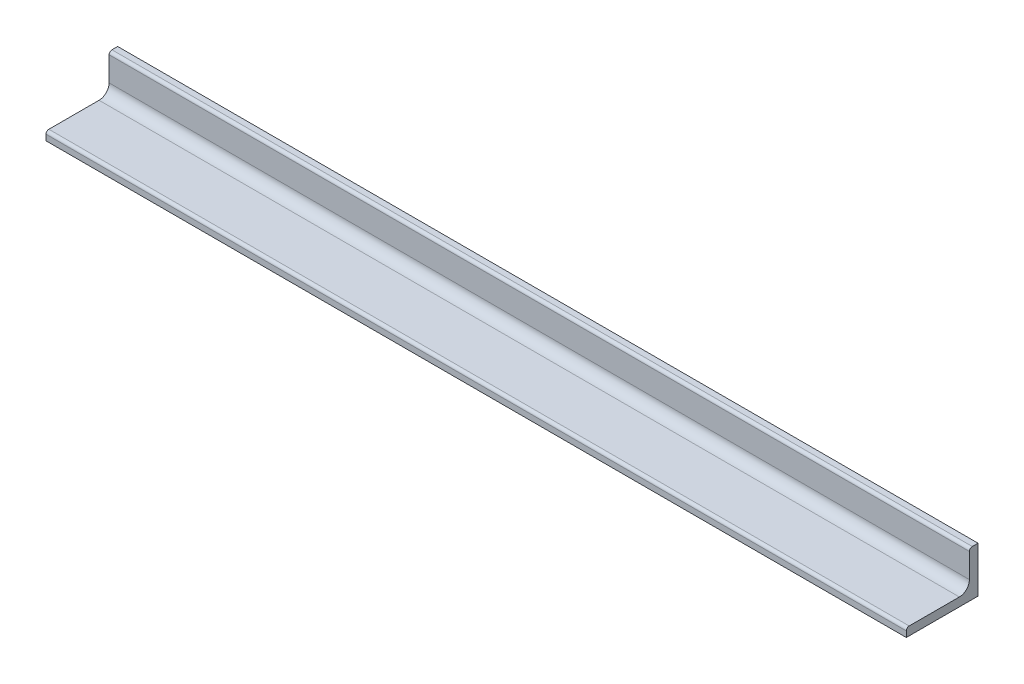
SolidWorks part; units mm, degrees
ref_plane "Front" through (0, 0, 0) normal (0, 0, 1) x (1, 0, 0)
ref_plane "Top" through (0, 0, 0) normal (0, 1, 0) x (1, 0, 0)
ref_plane "Right" through (0, 0, 0) normal (1, 0, 0) x (0, 0, -1)
sketch "Sketch1" plane through (0, 0, 0) normal (1, 0, 0) x (0, 1, 0)
  line L0 (0, 25) -> (0, 0)
  line L1 (0, 0) -> (16, 0)
  line L2 (3, 24) -> (3, 6.5)
  line L3 (6.5, 3) -> (15, 3)
  line L4 (0, 25) -> (2, 25)
  line L5 (16, 0) -> (16, 2)
  arc A0 (2, 25) -> (3, 24) centre (2, 24) cw
  arc A1 (16, 2) -> (15, 3) centre (15, 2) ccw
  arc A2 (3, 6.5) -> (6.5, 3) centre (6.5, 6.5) ccw
extrude "Base" add sketch "Sketch1" along normal blind 300
equation "\"r1@Sketch1\" = \"d@Sketch1\" / 3"
equation "\"d1@Sketch1\" = \"d@Sketch1\""
